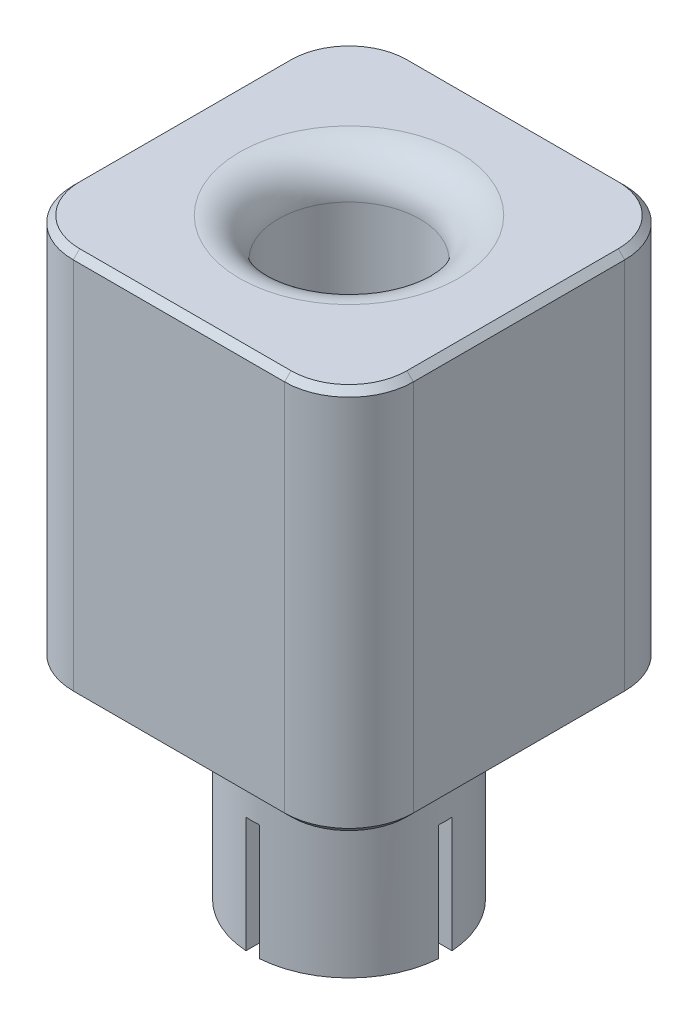
SolidWorks part; units mm, degrees
ref_plane "Front Plane" through (0, 0, 0) normal (0, 0, 1) x (1, 0, 0)
ref_plane "Top Plane" through (0, 0, 0) normal (0, 1, 0) x (1, 0, 0)
ref_plane "Right Plane" through (0, 0, 0) normal (1, 0, 0) x (0, 0, -1)
sketch "Sketch1" plane through (0, 0, 0) normal (0, 1, 0) x (1, 0, 0)
  circle A0 centre (0, 0) radius 3
  circle A1 centre (0, 0) radius 7.5
  dimension "D1" = 6
  dimension "D2" = 15
extrude "Boss-Extrude1" add sketch "Sketch1" along normal blind 6
sketch "Sketch2" plane through (0, 6, 0) normal (0, 1, 0) x (1, 0, 0)
  circle A0 centre (0, 0) radius 7.5
  circle A1 centre (0, 0) radius 5.5
  circle A2 centre (0, 0) radius 7.5 construction
  dimension "D1" = 11
extrude "Boss-Extrude2" add sketch "Sketch2" along normal blind 10
sketch "Sketch3" plane through (0, 0, 0) normal (0, -1, 0) x (1, 0, 0)
  line L1 (-10.4593, 0.5274) -> (10.4593, 0.5274)
  line L2 (-10.4593, 0.5274) -> (-10.4593, -0.5274)
  line L3 (-10.4593, -0.5274) -> (10.4593, -0.5274)
  line L4 (10.4593, 0.5274) -> (10.4593, -0.5274)
  line L5 (-10.4593, 0.5274) -> (10.4593, -0.5274) construction
  line L6 (-10.4593, -0.5274) -> (10.4593, 0.5274) construction
  line L7 (-0.5274, 10.5326) -> (0.5274, 10.5326)
  line L8 (-0.5274, 10.5326) -> (-0.5274, -10.5326)
  line L9 (-0.5274, -10.5326) -> (0.5274, -10.5326)
  line L10 (0.5274, 10.5326) -> (0.5274, -10.5326)
  line L11 (-0.5274, 10.5326) -> (0.5274, -10.5326) construction
  line L12 (-0.5274, -10.5326) -> (0.5274, 10.5326) construction
  point P0 (0, 0)
  point P6 (0, 0)
  circle M6 centre (0, 0) radius 7.5
  circle M7 centre (0, 0) radius 3
extrude "Cut-Extrude1" cut sketch "Sketch3" against normal blind 9 contours L10 L7 L8 M6 | L2 L3 L1 M6 | L10 L8 M6 M7 | L3 L1 M7 M6 | L10 L8 M7 M6 | L3 L1 M6 M7 region at (-8.9766, 0, 0) region at (-5.2391, 0, 0) region at (0, 0, 5.2391) region at (0, 0, 9.0132) region at (0, 0, -5.2391) region at (5.2391, 0, 0)
sketch "Sketch4" plane through (0, 16, 0) normal (0, 1, 0) x (1, 0, 0)
  line L1 (13.208, 13.208) -> (-13.208, 13.208)
  line L2 (13.208, 13.208) -> (13.208, -13.208)
  line L3 (13.208, -13.208) -> (-13.208, -13.208)
  line L4 (-13.208, 13.208) -> (-13.208, -13.208)
  line L5 (13.208, 13.208) -> (-13.208, -13.208) construction
  line L6 (13.208, -13.208) -> (-13.208, 13.208) construction
  circle A0 centre (0, 0) radius 5.5
  circle A1 centre (0, 0) radius 5.5 construction
  point P0 (0, 0)
  dimension "D1" = 26.416
extrude "Boss-Extrude3" add sketch "Sketch4" along normal blind 30
fillet "Fillet1" radius 3 1 edges at (0, 46, 5.5)
fillet "Fillet3" radius 5 4 edges at (13.208, 31, -13.208) (13.208, 31, 13.208) (-13.208, 31, 13.208) (-13.208, 31, -13.208)
chamfer "Chamfer1" distance 0.5 angle 45 16 edges at (-13.208, 46, 0) (0, 46, 13.208) (13.208, 46, 0) (0, 46, -13.208) (0, 16, -13.208) (13.208, 16, 0) (-13.208, 16, 0) (0, 16, 13.208) (-11.7435, 16, -11.7435) (11.7435, 16, -11.7435) (-11.7435, 16, 11.7435) (11.7435, 16, 11.7435) (11.7435, 46, 11.7435) (-11.7435, 46, 11.7435) (11.7435, 46, -11.7435) (-11.7435, 46, -11.7435)
chamfer "Chamfer2" distance 2.5 angle 45 4 edges at (-3.8891, 6, 3.8891) (3.8891, 6, 3.8891) (-3.8891, 6, -3.8891) (3.8891, 6, -3.8891)
fillet "Fillet2" radius 5 1 edges at (0, 16, 7.5)
